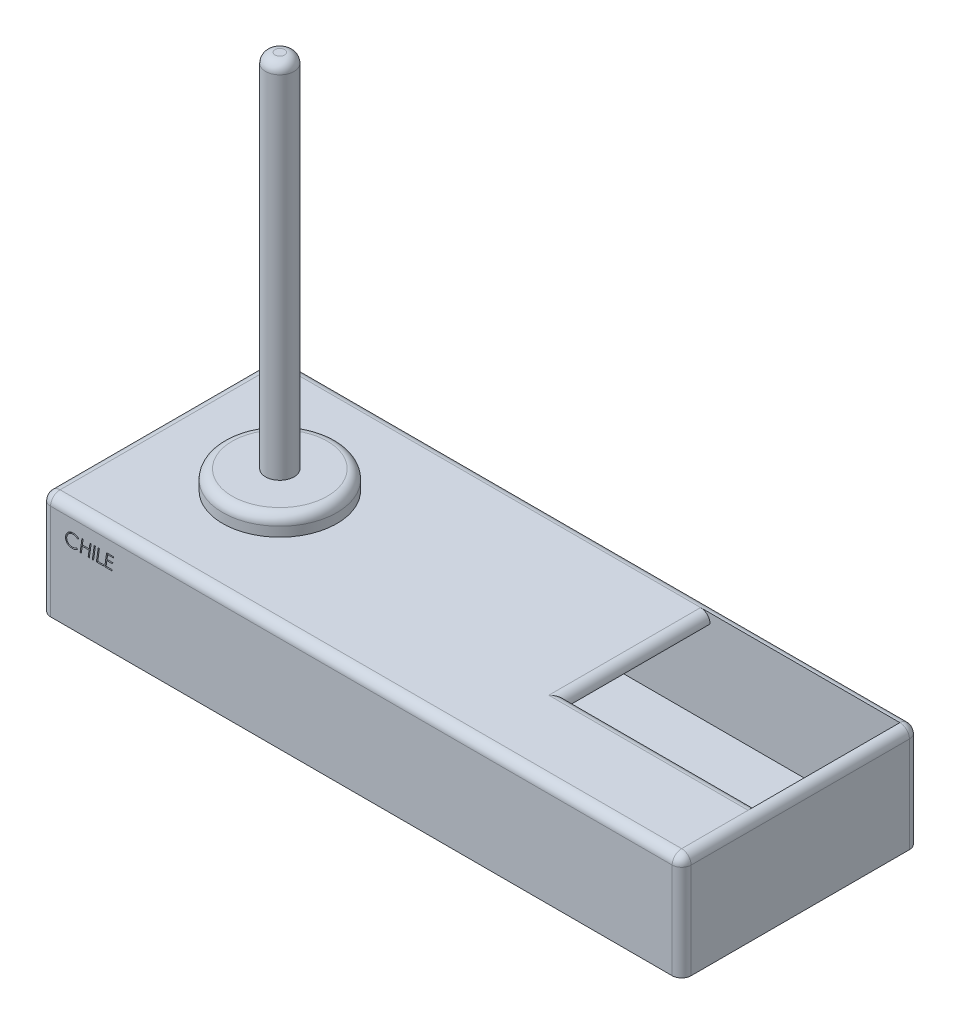
SolidWorks part; units mm, degrees
ref_plane "Front Plane" through (0, 0, 0) normal (0, 0, 1) x (1, 0, 0)
ref_plane "Top Plane" through (0, 0, 0) normal (0, 1, 0) x (1, 0, 0)
ref_plane "Right Plane" through (0, 0, 0) normal (1, 0, 0) x (0, 0, -1)
sketch "Sketch1" plane through (0, 0, 0) normal (0, 1, 0) x (1, 0, 0)
  line L1 (85.725, 31.75) -> (-85.725, 31.75)
  line L2 (85.725, 31.75) -> (85.725, -31.75)
  line L3 (85.725, -31.75) -> (-85.725, -31.75)
  line L4 (-85.725, 31.75) -> (-85.725, -31.75)
  line L5 (85.725, 31.75) -> (-85.725, -31.75) construction
  line L6 (85.725, -31.75) -> (-85.725, 31.75) construction
  point P0 (0, 0)
  dimension "D1" = 63.5
  dimension "D2" = 171.45
extrude "Boss-Extrude1" add sketch "Sketch1" along normal blind 28.194
shell "Shell1" thickness 2.54
fillet "Fillet1" radius 2.54 1 edges at (0, 28.194, -31.75)
fillet "Fillet2" radius 2.54 1 edges at (0, 28.194, 31.75)
fillet "Fillet3" radius 2.54 5 edges at (-85.725, 12.827, -31.75) (-85.725, 27.4501, -31.0061) (-85.725, 12.827, 31.75) (-85.725, 27.4501, 31.0061) (-85.725, 28.194, 0)
fillet "Fillet4" radius 2.54 5 edges at (85.725, 12.827, 31.75) (85.725, 27.4501, 31.0061) (85.725, 12.827, -31.75) (85.725, 27.4501, -31.0061) (85.725, 28.194, 0)
sketch "Sketch7" plane through (0, 28.194, 0) normal (0, 1, 0) x (1, 0, 0)
  line L1 (83.185, 29.21) -> (32.385, 29.21)
  line L2 (83.185, 29.21) -> (83.185, -8.89)
  line L3 (83.185, -8.89) -> (32.385, -8.89)
  line L4 (32.385, 29.21) -> (32.385, -8.89)
  dimension "D1" = 38.1
  dimension "D2" = 50.8
extrude "Cut-Extrude4" cut sketch "Sketch7" against normal up to next contours L2 L1 L4 L3
sketch "Sketch13" plane through (0, 28.194, 0) normal (0, 1, 0) x (1, 0, 0)
  circle A0 centre (-53.5798, 0) radius 3.81
  dimension "D1" = 7.62
extrude "Boss-Extrude3" add sketch "Sketch13" along normal blind 101.6
sketch "Sketch24" plane through (-85.725, 0, 0) normal (-1, 0, 0) x (0, 0, 1)
  line L0 (-29.21, 25.654) -> (-29.21, 0) construction
  line L1 (29.21, 25.654) -> (-29.21, 25.654)
  line L2 (29.21, 25.654) -> (29.21, 2.7797)
  line L3 (29.21, 2.7797) -> (-29.21, 2.7797)
  line L4 (-29.21, 25.654) -> (-29.21, 2.7797)
extrude "Cut-Extrude8" cut sketch "Sketch24" against normal up to next
sketch "Sketch25" plane through (0, 28.194, 0) normal (0, 1, 0) x (1, 0, 0)
  circle A0 centre (-53.5798, 0) radius 15.2885
extrude "Boss-Extrude4" add sketch "Sketch25" along normal blind 5.08
fillet "Fillet5" radius 2.54 1 edges at (-53.5798, 33.274, 15.2885)
fillet "Fillet6" radius 2.54 1 edges at (-53.5798, 129.794, 3.81)
fillet "Fillet7" radius 2.54 1 edges at (57.785, 28.194, 8.89)
fillet "Fillet8" radius 2.54 1 edges at (32.385, 28.194, -8.89)
sketch "Sketch28" plane through (0, 0, 31.75) normal (0, 0, 1) x (1, 0, 0)
  text T0 "<i>CHILE</i>"
extrude "Cut-Extrude13" cut sketch "Sketch28" against normal up to next
